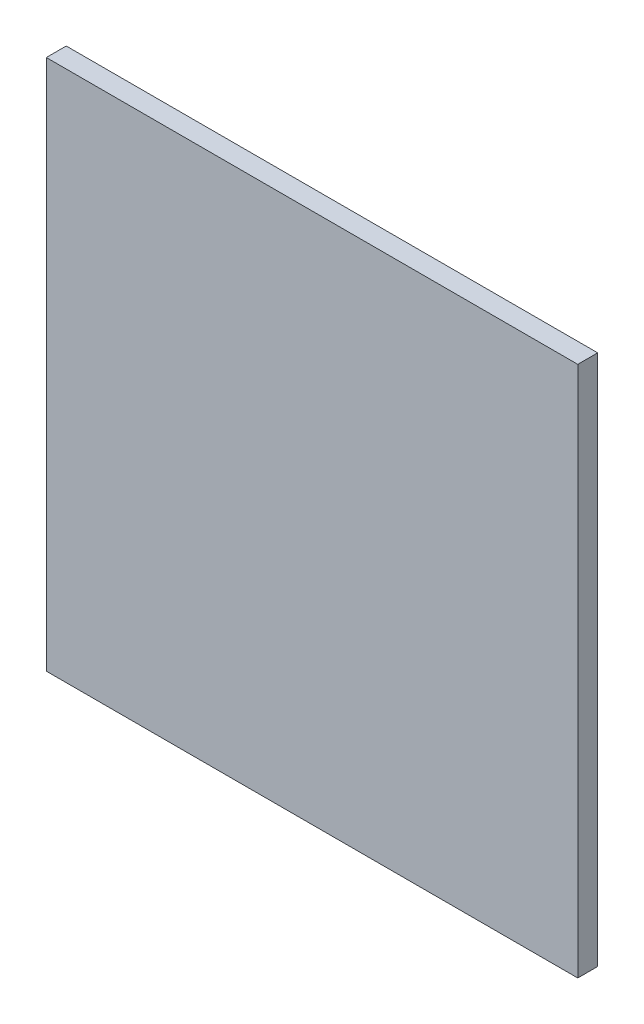
SolidWorks part; units mm, degrees
ref_plane "前视基准面" through (0, 0, 0) normal (0, 0, 1) x (1, 0, 0)
ref_plane "上视基准面" through (0, 0, 0) normal (0, 1, 0) x (1, 0, 0)
ref_plane "右视基准面" through (0, 0, 0) normal (1, 0, 0) x (0, 0, -1)
other "Configuration Table"
sketch "Sketch1" plane through (0, 0, 0) normal (0, 0, 1) x (1, 0, 0)
  line L1 (-400, -400) -> (400, -400)
  line L2 (-400, -400) -> (-400, 400)
  line L3 (-400, 400) -> (400, 400)
  line L4 (400, -400) -> (400, 400)
  line L5 (-400, -400) -> (400, 400) construction
  line L6 (-400, 400) -> (400, -400) construction
  point P0 (0, 0)
extrude "Boss-Extrude1" add sketch "Sketch1" along normal blind 30
sketch "Sketch2" plane through (0, 0, 0) normal (0, 0, 1) x (1, 0, 0)
  circle A0 centre (-325, -325) radius 10
  circle A1 centre (325, -325) radius 10
  circle A2 centre (-325, 325) radius 10
  circle A3 centre (325, 325) radius 10
extrude "Cut-Extrude1" cut sketch "Sketch2" along normal blind 15
ref_plane "bottom_face" through (0, 0, 0) normal (0, 0, 1) x (1, 0, 0)
ref_plane "top_face" through (0, 0, 30) normal (0, 0, 1) x (1, 0, 0)
sketch3d "3DSketch1"
  line L0 (-325, -325, 0) -> (-325, -325, 30) construction
ref_axis "hole_axis_front_left" through (-325, -325, 0) along (0, 0, 1)
sketch3d "3DSketch2"
  line L0 (325, -325, 0) -> (325, -325, 30) construction
ref_axis "hole_axis_front_right" through (325, -325, 0) along (0, 0, 1)
sketch3d "3DSketch3"
  line L0 (-325, 325, 0) -> (-325, 325, 30) construction
ref_axis "hole_axis_rear_left" through (-325, 325, 0) along (0, 0, 1)
sketch3d "3DSketch4"
  line L0 (325, 325, 0) -> (325, 325, 30) construction
ref_axis "hole_axis_rear_right" through (325, 325, 0) along (0, 0, 1)
